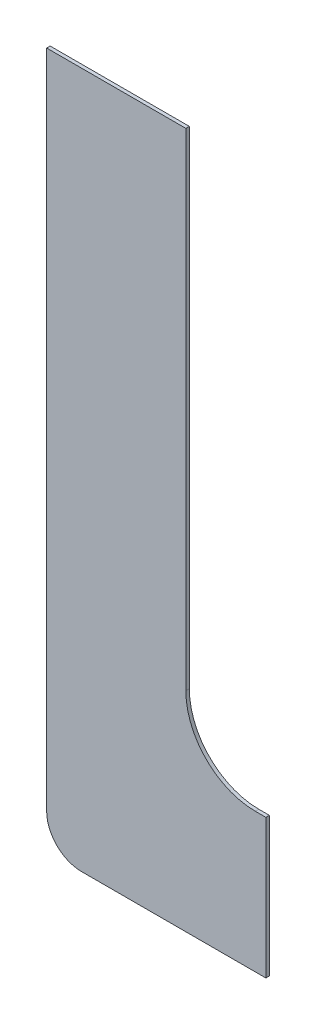
SolidWorks part; units mm, degrees
ref_plane "前视基准面" through (0, 0, 0) normal (0, 0, 1) x (1, 0, 0)
ref_plane "上视基准面" through (0, 0, 0) normal (0, 1, 0) x (1, 0, 0)
ref_plane "右视基准面" through (0, 0, 0) normal (1, 0, 0) x (0, 0, -1)
sketch "草图1" plane through (0, 0, 0) normal (0, 0, 1) x (1, 0, 0)
  line L0 (0, 0) -> (-31.5, 0)
  line L1 (-31.5, 0) -> (-31.5, 100)
  line L2 (-31.5, 100) -> (-11.5, 100)
  line L3 (-11.5, 100) -> (-11.5, 20)
  line L4 (-11.5, 20) -> (0, 20)
  line L5 (0, 20) -> (0, 0)
  dimension "D1" = 100
  dimension "D2" = 31.5
  dimension "D3" = 20
  dimension "D4" = 20
extrude "凸台-拉伸1" add sketch "草图1" along normal blind 0.5
fillet "圆角1" radius 10 1 edges at (-11.5, 20, 0.25)
fillet "圆角2" radius 5 1 edges at (-31.5, 0, 0.25)
sketch3d "3D草图1" [suppressed]
  line L0 (-11.5, 30, 0.5) -> (-11.5, 100, 0.5) construction
  arc A0 (-1.5, 20, 0.5) -> (-11.5, 30, 0.5) centre (-1.5, 30, 0.5) ccw construction
  point P0 (-1.5, 20, 0.5)
  point P1 (-8.5711, 22.9289, 0.5)
  point P3 (-11.5, 30, 0.5)
  point P7 (-1.5, 30, -9.5)
  point P8 (-11.5, 49.1552, 0.5)
  point P10 (-11.5, 87.2694, 0.5)
